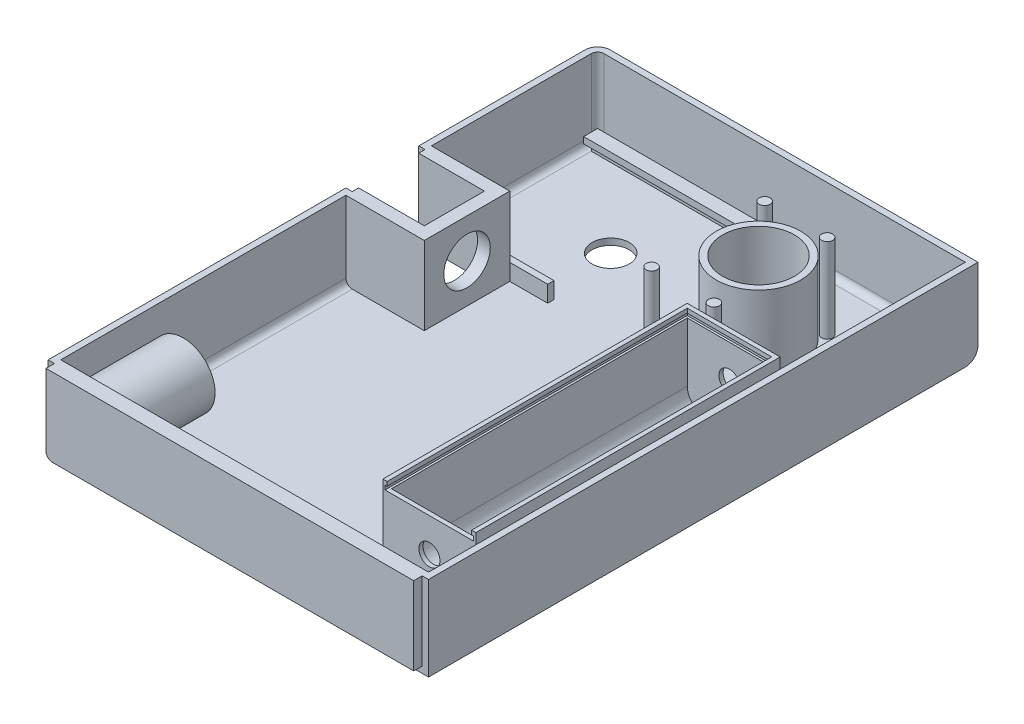
SolidWorks part; units mm, degrees
ref_plane "Front Plane" through (0, 0, 0) normal (0, 0, 1) x (1, 0, 0)
ref_plane "Top Plane" through (0, 0, 0) normal (0, 1, 0) x (1, 0, 0)
ref_plane "Right Plane" through (0, 0, 0) normal (1, 0, 0) x (0, 0, -1)
sketch "Sketch1" plane through (0, 0, 0) normal (0, 1, 0) x (1, 0, 0)
  line L1 (-58.2856, -26.3855) -> (-148.2856, -26.3855)
  line L2 (-58.2856, -26.3855) -> (-58.2856, 103.6145)
  line L3 (-58.2856, 103.6145) -> (-148.2856, 103.6145)
  line L4 (-148.2856, -26.3855) -> (-148.2856, 103.6145)
extrude "Boss-Extrude1" add sketch "Sketch1" along normal blind 20 contours L2 L1 L4 L3
fillet "Fillet1" radius 3 3 edges at (-148.2856, 0, -38.6145) (-103.2856, 0, -103.6145) (-148.2856, 10, -103.6145)
shell "Shell1" thickness 1.5 removed face at (-111.8099, 20, -51.1388)
sketch "Sketch2" plane through (0, 1.5, 0) normal (0, 1, 0) x (1, 0, 0)
  line L1 (-145.2856, 100.6145) -> (-99.2856, 100.6145)
  line L2 (-145.2856, 100.6145) -> (-145.2856, 97.3145)
  line L3 (-145.2856, 97.3145) -> (-99.2856, 97.3145)
  line L4 (-99.2856, 100.6145) -> (-99.2856, 97.3145)
  line L5 (-145.2856, -24.8855) -> (-145.2856, 100.6145) construction
  line L7 (-145.2856, 64.2991) -> (-119.2856, 64.2991)
  line L8 (-145.2856, 64.2991) -> (-145.2856, 62.7991)
  line L9 (-145.2856, 62.7991) -> (-119.2856, 62.7991)
  line L10 (-119.2856, 64.2991) -> (-119.2856, 62.7991)
  line M14 (-145.2856, 100.6145) -> (-145.2856, -24.8855)
extrude "Boss-Extrude2" add sketch "Sketch2" along normal blind 3.9 contours L10 L7 L9 M14 | L2 L1 L4 L3 region at (-132.2856, 1.5, -63.5491)
sketch3d "3DSketch2" plane through (0, 0, 0) normal (0, 0, 1) x (1, 0, 0)
sketch3d "3DSketch3"
  line L1 (-99.2856, 5.4, -97.3145) -> (-99.2856, 1.5, -97.3145) construction
  line L3 (-99.2856, 3.9, -97.3145) -> (-99.2856, 1.5, -97.3145)
  line L4 (-99.2856, 3.9, -97.3145) -> (-99.2856, 3.9, -99.1145)
  line L5 (-99.2856, 3.9, -99.1145) -> (-99.2856, 1.5, -99.1145)
  line L6 (-99.2856, 1.5, -97.3145) -> (-99.2856, 1.5, -99.1145)
extrude "Cut-Extrude1" cut sketch "3DSketch3" along direction (1, 0, 0) on the side of the normal up to surface (46 mm away) contours L4 L3 L6 L5
sketch "Sketch6" plane through (0, 1.5, 0) normal (0, 1, 0) x (1, 0, 0)
  circle A0 centre (-122.0856, 80.5081) radius 4.4
extrude "Cut-Extrude3" cut sketch "Sketch6" against normal up to surface (1.5 mm away) contours A0 up to face at (-101.7856, 0, -37.1145)
sketch "Sketch8" plane through (0, 1.5, 0) normal (0, 1, 0) x (1, 0, 0)
  circle A0 centre (-87.1063, 80.5081) radius 8.5
  circle A1 centre (-87.1063, 80.5081) radius 10
  circle A2 centre (-94.5641, 89.4081) radius 1.3
  circle A3 centre (-79.7641, 89.4081) radius 1.3
  circle A4 centre (-94.5027, 62.6081) radius 1.3
  circle A5 centre (-79.7641, 62.6081) radius 1.3
  point P9 (-94.5641, 89.4081)
sketch "Sketch10" plane through (0, 1.5, 0) normal (0, 1, 0) x (1, 0, 0)
extrude "Boss-Extrude7" add sketch "Sketch8" along normal blind 20
sketch "Sketch16" plane through (0, 21.5, 0) normal (0, 1, 0) x (1, 0, 0)
  circle A1 centre (-87.1063, 80.5081) radius 10
  circle A2 centre (-87.1063, 80.5081) radius 8.5
extrude "Cut-Extrude5" cut sketch "Sketch16" against normal up to surface (21.5 mm away) contours A2 up to face at (-122.0856, 0, -84.9081)
sketch "Sketch17" plane through (0, 21.5, 0) normal (0, 1, 0) x (1, 0, 0)
  circle A0 centre (-87.1063, 80.5081) radius 10
  circle A1 centre (-87.1063, 80.5081) radius 8.5
  circle M3 centre (-87.1063, 80.5081) radius 10
  circle M4 centre (-87.1063, 80.5081) radius 8.5
extrude "Boss-Extrude8" add sketch "Sketch17" against normal blind 3 contours M3 M4 | A0 region at (-96.8235, 21.5, -80.5081)
sketch "Sketch18" plane through (0, 21.5, 0) normal (0, 1, 0) x (1, 0, 0)
  circle A0 centre (-87.1063, 80.5081) radius 10.0086
extrude "Cut-Extrude6" cut sketch "Sketch18" against normal up to surface (3 mm away) contours A0 up to face at (-87.1063, 18.5, -72.0081)
sketch "Sketch19" plane through (0, 0, 0) normal (0, -1, 0) x (1, 0, 0)
  line L0 (-81.8577, -84.3424) -> (-84.6921, -81.5081)
  line L4 (-84.6921, -81.5081) -> (-80.6837, -81.5081)
  line L5 (-83.2719, -85.7566) -> (-86.1063, -82.9223)
  line L6 (-86.1063, -86.9307) -> (-86.1063, -82.9223)
  line L7 (-88.1063, -86.9307) -> (-88.1063, -82.9223)
  line L8 (-84.6921, -79.5081) -> (-80.6837, -79.5081)
  line L9 (-80.8577, -3.8344) -> (-83.6921, -1)
  line L10 (-90.9407, -85.7566) -> (-88.1063, -82.9223)
  line L11 (-92.3549, -84.3424) -> (-89.5205, -81.5081)
  line L12 (-89.5205, -81.5081) -> (-93.5289, -81.5081)
  line L13 (-81.8577, -76.6737) -> (-84.6921, -79.5081)
  line L14 (-86.1063, -74.0854) -> (-86.1063, -78.0938)
  line L15 (-83.2719, -75.2595) -> (-86.1063, -78.0938)
  line L16 (-90.9407, -75.2595) -> (-88.1063, -78.0938)
  line L17 (-88.1063, -74.0854) -> (-88.1063, -78.0938)
  line L18 (-92.3549, -76.6737) -> (-89.5205, -79.5081)
  line L19 (-89.5205, -79.5081) -> (-93.5289, -79.5081)
  line L20 (-83.6921, -1) -> (-79.6837, -1)
  line L21 (-82.2719, -5.2486) -> (-85.1063, -2.4142)
  line L22 (-85.1063, -6.4226) -> (-85.1063, -2.4142)
  line L23 (-87.1063, -6.4226) -> (-87.1063, -2.4142)
  line L24 (-83.6921, 1) -> (-79.6837, 1)
  line L25 (-89.9407, -5.2486) -> (-87.1063, -2.4142)
  line L26 (-91.3549, -3.8344) -> (-88.5205, -1)
  line L27 (-88.5205, -1) -> (-92.5289, -1)
  line L28 (-80.8577, 3.8344) -> (-83.6921, 1)
  line L29 (-85.1063, 6.4226) -> (-85.1063, 2.4142)
  line L30 (-82.2719, 5.2486) -> (-85.1063, 2.4142)
  line L31 (-89.9407, 5.2486) -> (-87.1063, 2.4142)
  line L32 (-87.1063, 6.4226) -> (-87.1063, 2.4142)
  line L33 (-91.3549, 3.8344) -> (-88.5205, 1)
  line L34 (-88.5205, 1) -> (-92.5289, 1)
  circle A0 centre (-87.1063, -80.5081) radius 8.5
  arc A3 (-88.1063, -86.9307) -> (-90.9407, -85.7566) centre (-87.1063, -80.5081) cw
  arc A4 (-92.3549, -84.3424) -> (-93.5289, -81.5081) centre (-87.1063, -80.5081) cw
  arc A5 (-81.8577, -84.3424) -> (-80.6837, -81.5081) centre (-87.1063, -80.5081) ccw
  arc A6 (-86.1063, -86.9307) -> (-83.2719, -85.7566) centre (-87.1063, -80.5081) ccw
  arc A7 (-81.8577, -76.6737) -> (-80.6837, -79.5081) centre (-87.1063, -80.5081) cw
  arc A8 (-86.1063, -74.0854) -> (-83.2719, -75.2595) centre (-87.1063, -80.5081) cw
  arc A9 (-88.1063, -74.0854) -> (-90.9407, -75.2595) centre (-87.1063, -80.5081) ccw
  arc A10 (-92.3549, -76.6737) -> (-93.5289, -79.5081) centre (-87.1063, -80.5081) ccw
  arc A11 (-87.1063, -6.4226) -> (-89.9407, -5.2486) centre (-86.1063, 0) cw
  arc A12 (-91.3549, -3.8344) -> (-92.5289, -1) centre (-86.1063, 0) cw
  arc A13 (-80.8577, -3.8344) -> (-79.6837, -1) centre (-86.1063, 0) ccw
  arc A14 (-85.1063, -6.4226) -> (-82.2719, -5.2486) centre (-86.1063, 0) ccw
  arc A15 (-80.8577, 3.8344) -> (-79.6837, 1) centre (-86.1063, 0) cw
  arc A16 (-85.1063, 6.4226) -> (-82.2719, 5.2486) centre (-86.1063, 0) cw
  arc A17 (-87.1063, 6.4226) -> (-89.9407, 5.2486) centre (-86.1063, 0) ccw
  arc A18 (-91.3549, 3.8344) -> (-92.5289, 1) centre (-86.1063, 0) ccw
extrude "Boss-Extrude12" add sketch "Sketch19" against normal blind 1
sketch "Sketch20" plane through (0, 1.5, 0) normal (0, 1, 0) x (1, 0, 0)
  line L0 (-77.1063, 80.5081) -> (-75.6063, 80.5081)
  line L1 (-68.4972, 100.6145) -> (-68.4972, 97.6145)
  line L2 (-99.2856, 100.6145) -> (-59.7856, 100.6145) construction
  line L3 (-75.3699, 97.3822) -> (-75.3699, 81.3822)
  line L8 (-75.3699, 81.3822) -> (-62.8699, 81.3822)
  line L9 (-62.8699, 97.3822) -> (-62.8699, 81.3822)
  line L10 (-75.1199, 97.1322) -> (-63.1199, 97.1322) construction
  line L11 (-75.1199, 97.1322) -> (-75.1199, 81.6322) construction
  line L12 (-75.1199, 81.6322) -> (-63.1199, 81.6322) construction
  line L13 (-63.1199, 97.1322) -> (-63.1199, 81.6322) construction
  line L14 (-75.3699, 97.3822) -> (-62.8699, 97.3822)
  line L19 (-76.6199, 98.6322) -> (-76.6199, 80.1322)
  line L20 (-76.6199, 80.1322) -> (-61.6199, 80.1322)
  line L21 (-61.6199, 98.6322) -> (-61.6199, 80.1322)
  line L22 (-76.6199, 98.6322) -> (-61.6199, 98.6322)
  line L24 (-76.6199, 98.6322) -> (-61.6199, 98.6322)
  line L25 (-76.6199, 98.6322) -> (-76.6199, 80.1322)
  line L26 (-76.6199, 80.1322) -> (-61.6199, 80.1322)
  line L27 (-61.6199, 98.6322) -> (-61.6199, 80.1322)
  line L28 (-75.3699, 97.3822) -> (-62.8699, 97.3822)
  line L29 (-75.3699, 97.3822) -> (-75.3699, 81.3822)
  line L30 (-75.3699, 81.3822) -> (-62.8699, 81.3822)
  line L31 (-62.8699, 97.3822) -> (-62.8699, 81.3822)
  line L32 (-75.1199, 97.1322) -> (-63.1199, 97.1322)
  line L33 (-75.1199, 97.1322) -> (-75.1199, 81.6322)
  line L34 (-75.1199, 81.6322) -> (-63.1199, 81.6322)
  line L35 (-63.1199, 97.1322) -> (-63.1199, 81.6322)
  circle A0 centre (-87.1063, 80.5081) radius 10 construction
  circle A4 centre (-69.0779, 76.0316) radius 1
  dimension "D1" = 1.5
extrude "Boss-Extrude15" add sketch "Sketch20" along normal blind 5.5 contours A4
sketch "Sketch21" plane through (0, 7, 0) normal (0, 1, 0) x (1, 0, 0)
  circle A1 centre (-69.0779, 76.0316) radius 0.7
extrude "Boss-Extrude16" add sketch "Sketch21" along normal blind 3
sketch "Sketch22" plane through (0, 1.5, 0) normal (0, 1, 0) x (1, 0, 0)
  line L1 (-76.6199, 98.6322) -> (-61.6199, 98.6322)
  line L2 (-76.6199, 98.6322) -> (-76.6199, 80.1322)
  line L3 (-76.6199, 80.1322) -> (-61.6199, 80.1322)
  line L4 (-61.6199, 98.6322) -> (-61.6199, 80.1322)
  line L5 (-75.3699, 97.3822) -> (-62.8699, 97.3822)
  line L6 (-75.3699, 97.3822) -> (-75.3699, 81.3822)
  line L7 (-75.3699, 81.3822) -> (-62.8699, 81.3822)
  line L8 (-62.8699, 97.3822) -> (-62.8699, 81.3822)
  line L9 (-75.1199, 97.1322) -> (-63.1199, 97.1322)
  line L10 (-75.1199, 97.1322) -> (-75.1199, 81.6322)
  line L11 (-75.1199, 81.6322) -> (-63.1199, 81.6322)
  line L12 (-63.1199, 97.1322) -> (-63.1199, 81.6322)
extrude "Cut-Extrude8" cut sketch "Sketch22" against normal blind 0.5 contours L10 L9 L12 L11
sketch "Sketch23" plane through (0, 1.5, 0) normal (0, 1, 0) x (1, 0, 0)
  line L1 (-76.6199, 98.6322) -> (-61.6199, 98.6322)
  line L2 (-76.6199, 98.6322) -> (-76.6199, 80.1322)
  line L3 (-76.6199, 80.1322) -> (-61.6199, 80.1322)
  line L4 (-61.6199, 98.6322) -> (-61.6199, 80.1322)
  line L5 (-75.3699, 97.3822) -> (-62.8699, 97.3822)
  line L6 (-75.3699, 97.3822) -> (-75.3699, 81.3822)
  line L7 (-75.3699, 81.3822) -> (-62.8699, 81.3822)
  line L8 (-62.8699, 97.3822) -> (-62.8699, 81.3822)
extrude "Boss-Extrude22" add sketch "Sketch23" along normal blind 1.5 contours L2 L1 L4 L3 | L6 L7 L8 L5
sketch "Sketch24" plane through (0, 1, 0) normal (0, 1, 0) x (1, 0, 0)
  line L3 (-71.6199, 95.6947) -> (-69.6199, 95.6947)
  line L36 (-69.6199, 96.6322) -> (-69.6199, 95.6947)
  line L84 (-71.6199, 96.6322) -> (-69.6199, 96.6322)
  line L85 (-71.6199, 96.6322) -> (-71.6199, 95.6947)
  line L86 (-63.6199, 95.6947) -> (-65.6199, 95.6947)
  line L87 (-63.6199, 94.6947) -> (-65.6199, 94.6947)
  line L88 (-63.6199, 91.8197) -> (-65.6199, 91.8197)
  line L89 (-63.6199, 90.8197) -> (-65.6199, 90.8197)
  line L90 (-66.6199, 95.6947) -> (-68.6199, 95.6947)
  line L91 (-66.6199, 94.6947) -> (-68.6199, 94.6947)
  line L92 (-66.6199, 91.8197) -> (-68.6199, 91.8197)
  line L93 (-66.6199, 90.8197) -> (-68.6199, 90.8197)
  line L94 (-71.6199, 93.7572) -> (-69.6199, 93.7572)
  line L95 (-63.6199, 96.6322) -> (-65.6199, 96.6322)
  line L96 (-63.6199, 96.6322) -> (-63.6199, 95.6947)
  line L97 (-63.6199, 95.6947) -> (-65.6199, 95.6947)
  line L98 (-65.6199, 96.6322) -> (-65.6199, 95.6947)
  line L99 (-63.6199, 94.6947) -> (-65.6199, 94.6947)
  line L100 (-63.6199, 94.6947) -> (-63.6199, 93.7572)
  line L101 (-63.6199, 93.7572) -> (-65.6199, 93.7572)
  line L102 (-65.6199, 94.6947) -> (-65.6199, 93.7572)
  line L103 (-63.6199, 92.7572) -> (-65.6199, 92.7572)
  line L104 (-63.6199, 92.7572) -> (-63.6199, 91.8197)
  line L105 (-63.6199, 91.8197) -> (-65.6199, 91.8197)
  line L106 (-65.6199, 92.7572) -> (-65.6199, 91.8197)
  line L107 (-63.6199, 90.8197) -> (-65.6199, 90.8197)
  line L108 (-63.6199, 90.8197) -> (-63.6199, 89.8822)
  line L109 (-63.6199, 89.8822) -> (-65.6199, 89.8822)
  line L110 (-65.6199, 90.8197) -> (-65.6199, 89.8822)
  line L111 (-66.6199, 92.7572) -> (-68.6199, 92.7572)
  line L112 (-66.6199, 92.7572) -> (-66.6199, 91.8197)
  line L113 (-66.6199, 91.8197) -> (-68.6199, 91.8197)
  line L114 (-68.6199, 92.7572) -> (-68.6199, 91.8197)
  line L115 (-66.6199, 90.8197) -> (-68.6199, 90.8197)
  line L116 (-66.6199, 90.8197) -> (-66.6199, 89.8822)
  line L117 (-66.6199, 89.8822) -> (-68.6199, 89.8822)
  line L118 (-68.6199, 90.8197) -> (-68.6199, 89.8822)
  line L119 (-66.6199, 96.6322) -> (-68.6199, 96.6322)
  line L120 (-66.6199, 96.6322) -> (-66.6199, 95.6947)
  line L121 (-66.6199, 95.6947) -> (-68.6199, 95.6947)
  line L122 (-68.6199, 96.6322) -> (-68.6199, 95.6947)
  line L123 (-66.6199, 94.6947) -> (-68.6199, 94.6947)
  line L124 (-66.6199, 94.6947) -> (-66.6199, 93.7572)
  line L125 (-66.6199, 93.7572) -> (-68.6199, 93.7572)
  line L126 (-68.6199, 94.6947) -> (-68.6199, 93.7572)
  line L127 (-69.6199, 94.6947) -> (-69.6199, 93.7572)
  line L128 (-71.6199, 94.6947) -> (-69.6199, 94.6947)
  line L129 (-71.6199, 94.6947) -> (-71.6199, 93.7572)
  line L130 (-71.6199, 91.8197) -> (-69.6199, 91.8197)
  line L131 (-69.6199, 92.7572) -> (-69.6199, 91.8197)
  line L132 (-71.6199, 92.7572) -> (-69.6199, 92.7572)
  line L133 (-71.6199, 92.7572) -> (-71.6199, 91.8197)
  line L134 (-71.6199, 89.8822) -> (-69.6199, 89.8822)
  line L135 (-69.6199, 90.8197) -> (-69.6199, 89.8822)
  line L136 (-71.6199, 90.8197) -> (-69.6199, 90.8197)
  line L137 (-71.6199, 90.8197) -> (-71.6199, 89.8822)
  line L138 (-74.6199, 89.8822) -> (-72.6199, 89.8822)
  line L139 (-72.6199, 90.8197) -> (-72.6199, 89.8822)
  line L140 (-74.6199, 90.8197) -> (-72.6199, 90.8197)
  line L141 (-74.6199, 90.8197) -> (-74.6199, 89.8822)
  line L142 (-74.6199, 91.8197) -> (-72.6199, 91.8197)
  line L143 (-72.6199, 92.7572) -> (-72.6199, 91.8197)
  line L144 (-74.6199, 92.7572) -> (-72.6199, 92.7572)
  line L145 (-74.6199, 92.7572) -> (-74.6199, 91.8197)
  line L146 (-74.6199, 93.7572) -> (-72.6199, 93.7572)
  line L147 (-72.6199, 94.6947) -> (-72.6199, 93.7572)
  line L148 (-74.6199, 94.6947) -> (-72.6199, 94.6947)
  line L149 (-74.6199, 94.6947) -> (-74.6199, 93.7572)
  line L150 (-74.6199, 95.6947) -> (-72.6199, 95.6947)
  line L151 (-72.6199, 96.6322) -> (-72.6199, 95.6947)
  line L152 (-74.6199, 96.6322) -> (-72.6199, 96.6322)
  line L153 (-74.6199, 96.6322) -> (-74.6199, 95.6947)
  line L154 (-63.6199, 88.8822) -> (-65.6199, 88.8822)
  line L155 (-65.6199, 87.9447) -> (-65.6199, 88.8822)
  line L156 (-63.6199, 87.9447) -> (-65.6199, 87.9447)
  line L157 (-63.6199, 87.9447) -> (-63.6199, 88.8822)
  line L158 (-63.6199, 87.9447) -> (-65.6199, 87.9447)
  line L159 (-71.6199, 87.9447) -> (-71.6199, 88.8822)
  line L160 (-71.6199, 87.9447) -> (-69.6199, 87.9447)
  line L161 (-69.6199, 87.9447) -> (-69.6199, 88.8822)
  line L162 (-71.6199, 88.8822) -> (-69.6199, 88.8822)
  line L163 (-74.6199, 82.1322) -> (-74.6199, 83.0697)
  line L164 (-74.6199, 82.1322) -> (-72.6199, 82.1322)
  line L165 (-72.6199, 82.1322) -> (-72.6199, 83.0697)
  line L166 (-74.6199, 83.0697) -> (-72.6199, 83.0697)
  line L167 (-74.6199, 84.0697) -> (-74.6199, 85.0072)
  line L168 (-74.6199, 84.0697) -> (-72.6199, 84.0697)
  line L169 (-72.6199, 84.0697) -> (-72.6199, 85.0072)
  line L170 (-74.6199, 85.0072) -> (-72.6199, 85.0072)
  line L171 (-74.6199, 86.0072) -> (-74.6199, 86.9447)
  line L172 (-74.6199, 86.0072) -> (-72.6199, 86.0072)
  line L173 (-72.6199, 86.0072) -> (-72.6199, 86.9447)
  line L174 (-74.6199, 86.9447) -> (-72.6199, 86.9447)
  line L175 (-74.6199, 87.9447) -> (-74.6199, 88.8822)
  line L176 (-74.6199, 87.9447) -> (-72.6199, 87.9447)
  line L177 (-72.6199, 87.9447) -> (-72.6199, 88.8822)
  line L178 (-74.6199, 88.8822) -> (-72.6199, 88.8822)
  line L179 (-71.6199, 86.0072) -> (-71.6199, 86.9447)
  line L180 (-71.6199, 86.0072) -> (-69.6199, 86.0072)
  line L181 (-69.6199, 86.0072) -> (-69.6199, 86.9447)
  line L182 (-71.6199, 86.9447) -> (-69.6199, 86.9447)
  line L183 (-71.6199, 84.0697) -> (-71.6199, 85.0072)
  line L184 (-71.6199, 84.0697) -> (-69.6199, 84.0697)
  line L185 (-69.6199, 84.0697) -> (-69.6199, 85.0072)
  line L186 (-71.6199, 85.0072) -> (-69.6199, 85.0072)
  line L187 (-71.6199, 82.1322) -> (-71.6199, 83.0697)
  line L188 (-71.6199, 82.1322) -> (-69.6199, 82.1322)
  line L189 (-69.6199, 82.1322) -> (-69.6199, 83.0697)
  line L190 (-71.6199, 83.0697) -> (-69.6199, 83.0697)
  line L191 (-66.6199, 83.0697) -> (-68.6199, 83.0697)
  line L192 (-68.6199, 82.1322) -> (-68.6199, 83.0697)
  line L193 (-66.6199, 82.1322) -> (-68.6199, 82.1322)
  line L194 (-66.6199, 82.1322) -> (-66.6199, 83.0697)
  line L195 (-66.6199, 85.0072) -> (-68.6199, 85.0072)
  line L196 (-68.6199, 84.0697) -> (-68.6199, 85.0072)
  line L197 (-66.6199, 84.0697) -> (-68.6199, 84.0697)
  line L198 (-66.6199, 84.0697) -> (-66.6199, 85.0072)
  line L199 (-66.6199, 86.9447) -> (-68.6199, 86.9447)
  line L200 (-68.6199, 86.0072) -> (-68.6199, 86.9447)
  line L201 (-66.6199, 86.0072) -> (-68.6199, 86.0072)
  line L202 (-66.6199, 86.0072) -> (-66.6199, 86.9447)
  line L203 (-66.6199, 88.8822) -> (-68.6199, 88.8822)
  line L204 (-68.6199, 87.9447) -> (-68.6199, 88.8822)
  line L205 (-66.6199, 87.9447) -> (-68.6199, 87.9447)
  line L206 (-66.6199, 87.9447) -> (-66.6199, 88.8822)
  line L207 (-63.6199, 86.9447) -> (-65.6199, 86.9447)
  line L208 (-65.6199, 86.0072) -> (-65.6199, 86.9447)
  line L209 (-63.6199, 86.0072) -> (-65.6199, 86.0072)
  line L210 (-63.6199, 86.0072) -> (-63.6199, 86.9447)
  line L211 (-63.6199, 85.0072) -> (-65.6199, 85.0072)
  line L212 (-65.6199, 84.0697) -> (-65.6199, 85.0072)
  line L213 (-63.6199, 84.0697) -> (-65.6199, 84.0697)
  line L214 (-63.6199, 84.0697) -> (-63.6199, 85.0072)
  line L215 (-63.6199, 83.0697) -> (-65.6199, 83.0697)
  line L216 (-65.6199, 82.1322) -> (-65.6199, 83.0697)
  line L217 (-63.6199, 82.1322) -> (-65.6199, 82.1322)
  line L218 (-63.6199, 82.1322) -> (-63.6199, 83.0697)
  point P64 (-70.6199, 87.9447)
extrude "Cut-Extrude11" cut sketch "Sketch24" against normal up to surface (1 mm away) contours L87 L102 L101 L100 | L103 L106 L88 L104 | L95 L98 L86 L96 | L119 L122 L90 L120 | L91 L126 L125 L124 | L111 L114 L92 L112 | L89 L110 L109 L108 | L156 L157 L154 L155 | L205 L206 L203 L204 | L93 L118 L117 L116 | L209 L210 L207 L208 | L201 L202 L199 L200 | L197 L198 L195 L196 | L213 L214 L211 L212 | L217 L218 L215 L216 | L193 L194 L191 L192 | L190 L187 L188 L189 | L186 L183 L184 L185 | L182 L179 L180 L181 | L162 L159 L160 L161 | L178 L175 L176 L177 | L174 L171 L172 L173 | L170 L167 L168 L169 | L166 L163 L164 L165 | L136 L137 L134 L135 | L140 L141 L138 L139 | L132 L133 L130 L131 | L144 L145 L142 L143 | L148 L149 L146 L147 | L128 L129 L94 L127 | L84 L85 L3 L36 | L152 L153 L150 L151 | L96 L95 L98 L97 | L85 L3 L36 L84 region at (-70.6199, 1, -96.1635) region at (-64.6199, 1, -96.1635) region at (-64.6199, 1, -94.226) region at (-64.6199, 1, -92.2885) region at (-64.6199, 1, -90.351) region at (-67.6199, 1, -96.1635) region at (-67.6199, 1, -94.226) region at (-67.6199, 1, -92.2885) region at (-67.6199, 1, -90.351) region at (-70.6199, 1, -94.226) region at (-70.6199, 1, -92.2885) region at (-70.6199, 1, -90.351) region at (-73.6199, 1, -90.351) region at (-73.6199, 1, -92.2885) region at (-73.6199, 1, -94.226) region at (-73.6199, 1, -96.1635) region at (-64.6199, 1, -88.4135) region at (-70.6199, 1, -88.4135) region at (-73.6199, 1, -82.601) region at (-73.6199, 1, -84.5385) region at (-73.6199, 1, -86.476) region at (-73.6199, 1, -88.4135) region at (-70.6199, 1, -86.476) region at (-70.6199, 1, -84.5385) region at (-70.6199, 1, -82.601) region at (-67.6199, 1, -82.601) region at (-67.6199, 1, -84.5385) region at (-67.6199, 1, -86.476) region at (-67.6199, 1, -88.4135) region at (-64.6199, 1, -86.476) region at (-64.6199, 1, -84.5385) region at (-64.6199, 1, -82.601) up to face at (-122.0856, 0, -84.9081)
sketch "Sketch25" plane through (0, 1.5, 0) normal (0, 1, 0) x (1, 0, 0)
  line L0 (-82.7641, 59.3081) -> (-82.7641, -12.6919)
  line L2 (-82.7641, -12.6919) -> (-60.7856, -12.6919)
  line L3 (-81.7641, 58.3081) -> (-61.7856, 58.3081)
  line L4 (-81.7641, 58.3081) -> (-81.7641, -11.6919)
  line L5 (-81.7641, -11.6919) -> (-61.7856, -11.6919)
  line L6 (-61.7856, 58.3081) -> (-61.7856, -11.6919)
  line L7 (-60.7856, 59.3081) -> (-60.7856, -12.6919)
  line L8 (-82.7641, 59.3081) -> (-60.7856, 59.3081)
extrude "Boss-Extrude25" add sketch "Sketch25" along normal blind 20 contours L6 L3 L4 L5 | L0 L2 L7 L8 region at (-71.7749, 1.5, -23.3081)
fillet "Fillet2" radius 4 2 edges at (-61.7856, 1.5, -23.3081) (-81.7641, 1.5, -23.3081)
sketch "Sketch31" plane through (0, 0, 12.6919) normal (0, 0, 1) x (1, 0, 0)
  circle A0 centre (-71.7749, 11.5) radius 2.5
extrude "Cut-Extrude12" cut sketch "Sketch31" against normal up to next
sketch "Sketch32" plane through (0, 0, -59.3081) normal (0, 0, -1) x (-1, 0, 0)
  circle A0 centre (71.7749, 11.5) radius 2.5
extrude "Cut-Extrude13" cut sketch "Sketch32" against normal up to next contours A0
sketch "Sketch34" plane through (0, 21.5, 0) normal (0, 1, 0) x (1, 0, 0)
  line L0 (-82.7641, -12.6919) -> (-60.7856, -12.6919) construction
  line L1 (-81.7641, -11.6919) -> (-61.7641, -11.6919)
  line L2 (-81.7641, -11.6919) -> (-81.7641, -12.6919)
  line L3 (-81.7641, -12.6919) -> (-61.7641, -12.6919)
  line L4 (-61.7641, -11.6919) -> (-61.7641, -12.6919)
extrude "Cut-Extrude14" cut sketch "Sketch34" against normal blind 2 contours L2 L1 L4 L3
sketch "Sketch35" plane through (-81.7641, 0, 0) normal (1, 0, 0) x (0, 0, -1)
  line L0 (58.3081, 21.5) -> (58.3081, 5.5) construction
  line L1 (-12.6919, 19.5) -> (58.3081, 19.5)
  line L2 (-12.6919, 19.5) -> (-12.6919, 20.5)
  line L3 (-12.6919, 20.5) -> (58.3081, 20.5)
  line L4 (58.3081, 19.5) -> (58.3081, 20.5)
extrude "Cut-Extrude15" cut sketch "Sketch35" against normal blind 0.5
sketch "Sketch36" plane through (-61.7641, 0, 0) normal (-1, 0, 0) x (0, 0, 1)
  line L1 (11.6919, 21.5) -> (12.6919, 21.5)
  line L2 (11.6919, 21.5) -> (11.6919, 19.5)
  line L3 (11.6919, 19.5) -> (12.6919, 19.5)
  line L4 (12.6919, 21.5) -> (12.6919, 19.5)
extrude "Boss-Extrude34" add sketch "Sketch36" along normal up to surface (0.0215 mm away) up to face at (-61.7856, 14.7, -16.3081)
sketch "Sketch38" plane through (-61.7856, 0, 0) normal (-1, 0, 0) x (0, 0, 1)
  line L0 (-58.3081, 21.5) -> (-58.3081, 5.5) construction
  line L1 (12.6919, 19.5) -> (-58.3081, 19.5)
  line L2 (12.6919, 19.5) -> (12.6919, 20.5)
  line L3 (12.6919, 20.5) -> (-58.3081, 20.5)
  line L4 (-58.3081, 19.5) -> (-58.3081, 20.5)
extrude "Cut-Extrude16" cut sketch "Sketch38" against normal blind 0.5
sketch "Sketch39" plane through (0, 0, -58.3081) normal (0, 0, 1) x (1, 0, 0)
  line L0 (-82.2641, 19.5) -> (-82.2641, 20.5) construction
  line L1 (-82.2641, 19.5) -> (-61.2856, 19.5)
  line L2 (-82.2641, 19.5) -> (-82.2641, 20.5)
  line L3 (-82.2641, 20.5) -> (-61.2856, 20.5)
  line L4 (-61.2856, 19.5) -> (-61.2856, 20.5)
  line L5 (-61.2856, 20.5) -> (-61.2856, 19.5) construction
sketch "Sketch40" plane through (-82.2641, 0, 0) normal (1, 0, 0) x (0, 0, -1)
extrude "Cut-Extrude17" cut sketch "Sketch39" against normal blind 0.5
sketch "Sketch41" plane through (0, 0, 24.8855) normal (0, 0, -1) x (-1, 0, 0)
  circle A0 centre (137.7856, 11.5) radius 3
  circle A1 centre (137.7856, 11.5) radius 6.5
  circle A2 centre (137.7856, 11.5) radius 7.5
sketch "Sketch42" plane through (0, 0, 24.8855) normal (0, 0, -1) x (-1, 0, 0)
  line L0 (140.7856, 11.5) -> (134.7856, 11.5)
  circle A0 centre (137.7856, 11.5) radius 3 construction
  circle A1 centre (137.7856, 11.5) radius 6.5
  circle A2 centre (137.7856, 11.5) radius 7.5
extrude "Boss-Extrude35" add sketch "Sketch42" along normal blind 20 contours A2 A1 region at (-130.4978, 11.5, 24.8855)
sketch "Sketch45" plane through (-148.2856, 0, 0) normal (-1, 0, 0) x (0, 0, 1)
  line L2 (26.3855, 20) -> (-100.6145, 20) construction
  line L3 (-62.6145, 20) -> (-42.6145, 20)
  line L4 (-62.6145, 20) -> (-62.6145, 3)
  line L5 (-62.6145, 3) -> (-42.6145, 3)
  line L6 (-42.6145, 20) -> (-42.6145, 3)
  line L7 (-100.6145, 3) -> (26.3855, 3) construction
extrude "Cut-Extrude19" cut sketch "Sketch45" against normal up to surface (1.5 mm away) contours L4 L3 L6 L5 up to face at (-146.7856, 11.5, -37.8645)
sketch "Sketch48" plane through (0, 3, 0) normal (0, 1, 0) x (1, 0, 0)
  line L1 (-148.2856, 62.6145) -> (-128.2455, 62.6145)
  line L2 (-148.2856, 62.6145) -> (-148.2856, 42.5758)
  line L3 (-148.2856, 42.5758) -> (-128.2455, 42.5758)
  line L4 (-128.2455, 62.6145) -> (-128.2455, 42.5758)
extrude "Cut-Extrude20" cut sketch "Sketch48" against normal through all contours L2 L1 L4 L3
sketch "Sketch49" plane through (0, 0, -62.6145) normal (0, 0, 1) x (1, 0, 0)
  line L1 (-128.2455, 0) -> (-148.2856, 0)
  line L2 (-128.2455, 0) -> (-128.2455, 20)
  line L3 (-128.2455, 20) -> (-148.2856, 20)
  line L4 (-148.2856, 0) -> (-148.2856, 20)
extrude "Cut-Extrude22" cut sketch "Sketch49" against normal up to surface (0.1846 mm away) contours L2 L1 L4 L3 up to face at (-132.2856, 3.45, -62.7991)
sketch "Sketch52" plane through (0, 0, 0) normal (0, -1, 0) x (-1, 0, 0)
  line L1 (128.2455, 62.7991) -> (148.2856, 62.7991)
  line L2 (128.2455, 62.7991) -> (128.2455, 42.5758)
  line L3 (128.2455, 42.5758) -> (148.2856, 42.5758)
  line L4 (148.2856, 62.7991) -> (148.2856, 42.5758)
extrude "Boss-Extrude37" add sketch "Sketch52" against normal up to surface (20 mm away) up to face at (-121.9951, 20, -51.5646)
sketch "Sketch54" plane through (0, 20, 0) normal (0, 1, 0) x (1, 0, 0)
  line L0 (-128.2455, 44.0758) -> (-129.7455, 44.0758)
  line L1 (-128.2455, 42.5758) -> (-128.2455, 44.0758)
  line L2 (-128.2455, 42.5758) -> (-128.2455, 62.7991) construction
  line L3 (-146.7856, 62.7991) -> (-146.7856, 61.2991)
  line L4 (-148.2856, -26.3855) -> (-148.2856, 100.6145) construction
  line L9 (-129.7455, 61.2991) -> (-148.2856, 61.2991)
  line L10 (-129.7455, 61.2991) -> (-129.7455, 44.0758)
  line L11 (-129.7455, 44.0758) -> (-148.2856, 44.0758)
  line L12 (-148.2856, 61.2991) -> (-148.2856, 44.0758)
  dimension "D1" = 1.5
  dimension "D2" = 1.5
  dimension "D3" = 1.5
extrude "Cut-Extrude23" cut sketch "Sketch54" against normal up to surface (20 mm away) contours L10 L9 L12 L11 up to face at (-124.2856, 0, -44.901)
fillet "Fillet8" radius 3 1 edges at (-148.2856, 0, -62.0491)
fillet "Fillet9" radius 3 1 edges at (-148.2856, 0, -43.3258)
sketch "Sketch56" plane through (0, 0, -61.2991) normal (0, 0, 1) x (1, 0, 0)
  line L8 (-146.7856, 18.5) -> (-146.7856, 3)
  line L9 (-145.2856, 1.5) -> (-131.2455, 1.5)
  line L10 (-131.2455, 1.5) -> (-131.2455, 18.5)
  line L11 (-131.2455, 18.5) -> (-146.7856, 18.5)
  line L12 (-146.7856, 18.5) -> (-146.7856, 3)
  line L13 (-145.2856, 1.5) -> (-131.2455, 1.5)
  line L14 (-131.2455, 1.5) -> (-131.2455, 18.5)
  line L15 (-131.2455, 18.5) -> (-146.7856, 18.5)
  arc A2 (-146.7856, 3) -> (-145.2856, 1.5) centre (-145.2856, 3) ccw
  arc A3 (-146.7856, 3) -> (-145.2856, 1.5) centre (-145.2856, 3) ccw
  dimension "D1" = 1.5
extrude "Boss-Extrude39" add sketch "Sketch56" along normal blind 1 contours L12 A3 L13 L14 L15
sketch "Sketch57" plane through (0, 18.5, 0) normal (0, 1, 0) x (1, 0, 0)
  line L1 (-131.2455, 61.2991) -> (-146.7856, 61.2991)
  line L2 (-131.2455, 61.2991) -> (-131.2455, 60.2991)
  line L3 (-131.2455, 60.2991) -> (-146.7856, 60.2991)
  line L4 (-146.7856, 61.2991) -> (-146.7856, 60.2991)
extrude "Boss-Extrude40" add sketch "Sketch57" along normal up to surface (1.5 mm away) contours L2 L1 L4 L3 up to face at (-123.2001, 20, -51.7926)
sketch "Sketch58" plane through (-129.7455, 0, 0) normal (-1, 0, 0) x (0, 0, 1)
  line L0 (-44.0758, 0) -> (-44.0758, 20) construction
  line L1 (-61.2991, 20) -> (-44.0758, 20)
  line L2 (-61.2991, 20) -> (-61.2991, 1.5)
  line L3 (-61.2991, 1.5) -> (-44.0758, 1.5)
  line L4 (-44.0758, 20) -> (-44.0758, 1.5)
extrude "Boss-Extrude41" add sketch "Sketch58" along normal blind 1.5 contours L2 L1 L4 L3
sketch "Sketch59" plane through (0, 0, -44.0758) normal (0, 0, -1) x (-1, 0, 0)
  line L12 (132.7455, 18.5) -> (132.7455, 1.5)
  line L13 (132.7455, 1.5) -> (145.2856, 1.5)
  line L14 (146.7856, 3) -> (146.7856, 18.5)
  line L15 (146.7856, 18.5) -> (132.7455, 18.5)
  line L16 (132.7455, 18.5) -> (132.7455, 1.5)
  line L17 (132.7455, 1.5) -> (145.2856, 1.5)
  line L18 (146.7856, 3) -> (146.7856, 18.5)
  line L19 (146.7856, 18.5) -> (132.7455, 18.5)
  arc A2 (145.2856, 1.5) -> (146.7856, 3) centre (145.2856, 3) ccw
  arc A3 (145.2856, 1.5) -> (146.7856, 3) centre (145.2856, 3) ccw
  dimension "D1" = 1.5
extrude "Boss-Extrude42" add sketch "Sketch59" along normal blind 1.5 contours L16 L17 A3 L18 L19
sketch "Sketch62" plane through (0, 18.5, 0) normal (0, 1, 0) x (1, 0, 0)
  line L1 (-132.7455, 45.5758) -> (-146.7856, 45.5758)
  line L2 (-132.7455, 45.5758) -> (-132.7455, 44.0758)
  line L3 (-132.7455, 44.0758) -> (-146.7856, 44.0758)
  line L4 (-146.7856, 45.5758) -> (-146.7856, 44.0758)
extrude "Boss-Extrude43" add sketch "Sketch62" along normal up to surface (1.5 mm away) contours L2 L1 L4 L3 up to face at (-128.3348, 20, -53.3675)
sketch "Sketch66" plane through (-132.7455, 0, 0) normal (1, 0, 0) x (0, 0, -1)
  line L1 (45.5758, 1.5) -> (44.0758, 1.5)
  line L2 (45.5758, 1.5) -> (45.5758, 20)
  line L3 (45.5758, 20) -> (44.0758, 20)
  line L4 (44.0758, 1.5) -> (44.0758, 20)
extrude "Boss-Extrude44" add sketch "Sketch66" along normal up to surface (1.5 mm away) contours L2 L1 L4 L3 up to face at (-131.2455, 10.75, -52.1875)
sketch "Sketch67" plane through (0, 1.5, 0) normal (0, -1, 0) x (1, 0, 0)
  line L2 (-129.7455, -49.6875) -> (-130.4955, -49.6875)
  line L3 (-129.7455, -55.6875) -> (-130.4955, -55.6875)
  line L5 (-130.4955, -49.6875) -> (-129.7455, -49.6875)
  line L6 (-130.4955, -49.6875) -> (-130.4955, -55.6875)
  line L7 (-130.4955, -55.6875) -> (-129.7455, -55.6875)
  line L8 (-129.7455, -49.6875) -> (-129.7455, -55.6875)
  line M7 (-129.7455, -61.2991) -> (-129.7455, -44.0758)
extrude "Cut-Extrude24" cut sketch "Sketch67" against normal blind 1 contours L2 L6 L3 M7 region at (-130.1205, 1.5, -52.6875)
fillet "Fillet10" radius 0.25 1 edges at (-130.4955, 1.5, -52.6875)
sketch "Sketch69" plane through (0, 0, -60.2991) normal (0, 0, 1) x (1, 0, 0)
  line L8 (-131.2455, 1.5) -> (-131.2455, 20)
  line L9 (-131.2455, 20) -> (-146.7856, 20)
  line L10 (-146.7856, 20) -> (-146.7856, 3)
  line L11 (-145.2856, 1.5) -> (-131.2455, 1.5)
  line L12 (-131.2455, 1.5) -> (-131.2455, 20)
  line L13 (-131.2455, 20) -> (-146.7856, 20)
  line L14 (-146.7856, 20) -> (-146.7856, 3)
  line L15 (-145.2856, 1.5) -> (-131.2455, 1.5)
  arc A2 (-146.7856, 3) -> (-145.2856, 1.5) centre (-145.2856, 3) ccw
  arc A3 (-146.7856, 3) -> (-145.2856, 1.5) centre (-145.2856, 3) ccw
  dimension "D1" = 0
extrude "Boss-Extrude45" add sketch "Sketch69" along normal blind 0.5
sketch "Sketch70" plane through (-131.2455, 0, 0) normal (-1, 0, 0) x (0, 0, 1)
  circle A0 centre (-52.6875, 10.75) radius 5.5
extrude "Cut-Extrude26" cut sketch "Sketch70" against normal up to next
sketch "Sketch73" plane through (0, 0, 26.3855) normal (0, 0, 1) x (1, 0, 0)
  line L8 (-146.7856, 18.5) -> (-146.7856, 3)
  line L9 (-145.2856, 1.5) -> (-59.7856, 1.5)
  line L10 (-59.7856, 1.5) -> (-59.7856, 18.5)
  line L11 (-59.7856, 18.5) -> (-146.7856, 18.5)
  line L12 (-146.7856, 18.5) -> (-146.7856, 3)
  line L13 (-145.2856, 1.5) -> (-59.7856, 1.5)
  line L14 (-59.7856, 1.5) -> (-59.7856, 18.5)
  line L15 (-59.7856, 18.5) -> (-146.7856, 18.5)
  arc A2 (-146.7856, 3) -> (-145.2856, 1.5) centre (-145.2856, 3) ccw
  arc A3 (-146.7856, 3) -> (-145.2856, 1.5) centre (-145.2856, 3) ccw
  point P0 (0, 0)
  dimension "D1" = 1.5
extrude "Boss-Extrude48" add sketch "Sketch73" along normal blind 2 contours L12 A3 L13 L14 L15
sketch "Sketch74" plane through (0, 18.5, 0) normal (0, 1, 0) x (1, 0, 0)
  line L8 (-59.7856, -26.3855) -> (-146.7856, -26.3855)
  line L9 (-146.7856, -26.3855) -> (-146.7856, -28.3855)
  line L10 (-146.7856, -28.3855) -> (-59.7856, -28.3855)
  line L11 (-59.7856, -28.3855) -> (-59.7856, -26.3855)
  line L12 (-59.7856, -26.3855) -> (-146.7856, -26.3855)
  line L13 (-146.7856, -26.3855) -> (-146.7856, -28.3855)
  line L14 (-146.7856, -28.3855) -> (-59.7856, -28.3855)
  line L15 (-59.7856, -28.3855) -> (-59.7856, -26.3855)
  dimension "D1" = 0
extrude "Boss-Extrude49" add sketch "Sketch74" along normal blind 1.5 contours L12 L13 L14 L15
sketch "Sketch75" plane through (0, 0, 28.3855) normal (0, 0, 1) x (1, 0, 0)
  line L0 (-137.8628, 11.463) -> (-107.8628, 11.463)
  line L1 (-107.8628, 11.463) -> (-107.8628, 1.5)
  line L2 (-145.2856, 1.5) -> (-59.7856, 1.5) construction
  line L3 (-107.8628, 1.5) -> (-107.8628, 16.5)
  point P2 (0, 0)
  dimension "D1" = 30
